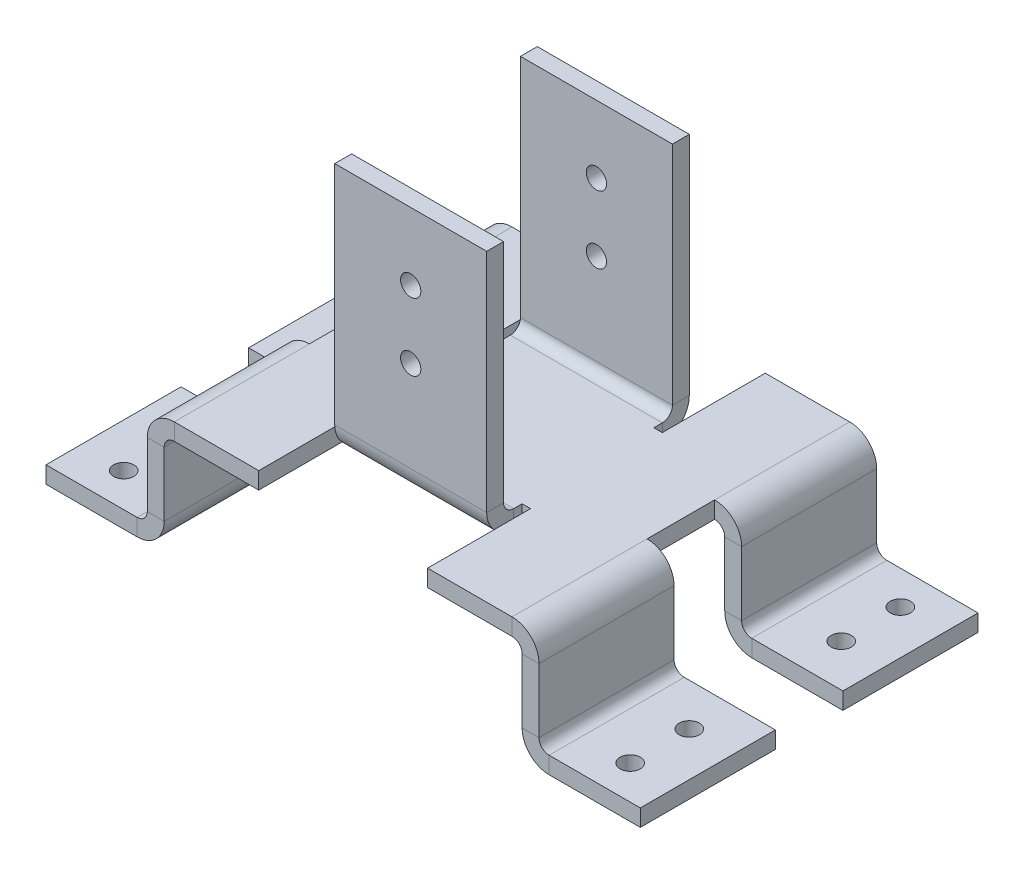
SolidWorks part; units mm, degrees
note: The reader was unsure of these and kept them because the rebuilt part matched: flange length of "边线-法兰1", "边线-法兰2", "边线-法兰14", "边线-法兰15", "边线-法兰16", "边线-法兰17", "边线-法兰18", "边线-法兰19", "边线-法兰20", "边线-法兰21".
ref_plane "前视基准面" through (0, 0, 0) normal (0, 0, 1) x (1, 0, 0)
ref_plane "上视基准面" through (0, 0, 0) normal (0, 1, 0) x (1, 0, 0)
ref_plane "右视基准面" through (0, 0, 0) normal (1, 0, 0) x (0, 0, -1)
other "Configuration Table"
sketch "草图1" plane through (0, 0, 0) normal (0, 1, 0) x (1, 0, 0)
  line L0 (-25, -25) -> (-25, -50)
  line L5 (-50, -50) -> (50, -50) construction
  line L6 (-50, -50) -> (-50, 50)
  line L11 (-50, 50) -> (50, 50) construction
  line L12 (50, -50) -> (50, 50)
  line L13 (-50, -50) -> (50, 50) construction
  line L14 (-50, 50) -> (50, -50) construction
  line L15 (-25, -25) -> (25, -25)
  line L16 (-25, -25) -> (-25, 25) construction
  line L17 (-25, 25) -> (25, 25)
  line L18 (25, -25) -> (25, 25) construction
  line L19 (-25, -25) -> (25, 25) construction
  line L20 (-25, 25) -> (25, -25) construction
  line L21 (-25, -50) -> (-50, -50)
  line L22 (25, -25) -> (25, -50)
  line L23 (25, -50) -> (50, -50)
  line L24 (-25, 25) -> (-25, 50)
  line L25 (-25, 50) -> (-50, 50)
  line L26 (25, 25) -> (25, 50)
  line L27 (25, 50) -> (50, 50)
  point P0 (0, 0)
  point P6 (0, 0)
  dimension "D1" = 100
  dimension "D2" = 100
  dimension "D3" = 50
base flange "基体-法兰1" sketch "草图1" thickness 5 reverse thickness direction no parameters "D1"=0.7366
edge flange "边线-法兰1" sketch "草图8" flange angle 90 flange length 75 flange position material outside bend radius 3 thickness 5 relief rectangular parameters "D6"=10
sketch "草图8" plane through (0, 0, -25) normal (0, 0, -1) x (-1, 0, 0)
  line L1 (-22.5, 0) -> (22.5, 0)
  line L2 (-22.5, 0) -> (-22.5, 70)
  line L3 (-22.5, 70) -> (22.5, 70)
  line L4 (22.5, 0) -> (22.5, 70)
  line L5 (-25, 0) -> (25, 0) construction
  point P6 (0, 70)
  dimension "D1" = 70
  dimension "D2" = 45
bend "边线折弯1" bend radius 3 bend angle 90 parameters "D5"=1
edge flange "边线-法兰2" sketch "草图11" flange angle 90 flange length 75 flange position material outside bend radius 3 thickness 5 relief rectangular parameters "D6"=10
sketch "草图11" plane through (0, 0, 25) normal (0, 0, 1) x (1, 0, 0)
  line L6 (-22.5, 70) -> (22.5, 70)
  line L7 (-22.5, 70) -> (-22.5, 0)
  line L8 (-22.5, 0) -> (22.5, 0)
  line L9 (22.5, 70) -> (22.5, 0)
bend "边线折弯2" bend radius 3 bend angle 90 parameters "D5"=2
edge flange "边线-法兰14" sketch "草图54" flange angle 90 flange length 35 flange position bend outside bend radius 3 thickness 5 relief rectangular parameters "D6"=10
sketch "草图54" plane through (50, -5, 0) normal (1, 0, 0) x (0, 0, 1)
  line L6 (50, 0) -> (10, 0)
  line L7 (50, 0) -> (50, 30)
  line L8 (50, 30) -> (10, 30)
  line L9 (10, 0) -> (10, 30)
  dimension "D1" = 30
  dimension "D2" = 40
bend "边线折弯12" bend radius 3 bend angle 90 parameters "D5"=3
edge flange "边线-法兰15" sketch "草图57" flange angle 90 flange length 35 flange position bend outside bend radius 3 thickness 5 relief rectangular parameters "D6"=10
sketch "草图57" plane through (50, -5, 0) normal (1, 0, 0) x (0, 0, 1)
  line L6 (-50, 0) -> (-10, 0)
  line L7 (-50, 0) -> (-50, 30)
  line L8 (-50, 30) -> (-10, 30)
  line L9 (-10, 0) -> (-10, 30)
  dimension "D1" = 40
  dimension "D2" = 30
bend "边线折弯13" bend radius 3 bend angle 90 parameters "D5"=4
edge flange "边线-法兰16" sketch "草图62" flange angle 90 flange length 35 flange position bend outside bend radius 3 thickness 5 relief rectangular parameters "D6"=10
sketch "草图62" plane through (-50, -5, 0) normal (-1, 0, 0) x (0, 0, -1)
  line L6 (50, 0) -> (10, 0)
  line L7 (50, 0) -> (50, 30)
  line L8 (50, 30) -> (10, 30)
  line L9 (10, 0) -> (10, 30)
bend "边线折弯14" bend radius 3 bend angle 90 parameters "D5"=5
edge flange "边线-法兰17" sketch "草图65" flange angle 90 flange length 35 flange position bend outside bend radius 3 thickness 5 relief rectangular parameters "D6"=10
sketch "草图65" plane through (-50, -5, 0) normal (-1, 0, 0) x (0, 0, -1)
  line L6 (-50, 0) -> (-10, 0)
  line L7 (-50, 0) -> (-50, 30)
  line L8 (-50, 30) -> (-10, 30)
  line L9 (-10, 0) -> (-10, 30)
bend "边线折弯15" bend radius 3 bend angle 90 parameters "D5"=6
edge flange "边线-法兰18" sketch "草图70" flange angle 90 flange length 35 bend radius 3 thickness 5 relief rectangular parameters "D6"=10
sketch "草图70" plane through (-58, -35, 0) normal (0, -1, 0) x (0, 0, 1)
  line L0 (-50, 0) -> (-10, 0) construction
  line L1 (-50, 0) -> (-10, 0)
  line L2 (-50, 0) -> (-50, 30)
  line L3 (-50, 30) -> (-10, 30)
  line L4 (-10, 30) -> (-10, 0)
  dimension "D1" = 30
bend "边线折弯16" bend radius 3 bend angle 90 parameters "D5"=7
edge flange "边线-法兰19" sketch "草图73" flange angle 90 flange length 35 bend radius 3 thickness 5 relief rectangular parameters "D6"=10
sketch "草图73" plane through (-58, -35, 0) normal (0, -1, 0) x (0, 0, 1)
  line L0 (10, 0) -> (50, 0) construction
  line L1 (10, 0) -> (50, 0)
  line L2 (10, 0) -> (10, 30)
  line L3 (10, 30) -> (50, 30)
  line L4 (50, 30) -> (50, 0)
  dimension "D1" = 30
bend "边线折弯17" bend radius 3 bend angle 90 parameters "D5"=8
edge flange "边线-法兰20" sketch "草图76" flange angle 90 flange length 35 bend radius 3 thickness 5 relief rectangular parameters "D6"=10
sketch "草图76" plane through (58, -35, 0) normal (0, -1, 0) x (0, 0, -1)
  line L0 (-50, 0) -> (-10, 0) construction
  line L1 (-50, 0) -> (-10, 0)
  line L2 (-50, 0) -> (-50, 30)
  line L3 (-50, 30) -> (-10, 30)
  line L4 (-10, 30) -> (-10, 0)
  dimension "D1" = 30
bend "边线折弯18" bend radius 3 bend angle 90 parameters "D5"=9
edge flange "边线-法兰21" sketch "草图79" flange angle 90 flange length 35 bend radius 3 thickness 5 relief rectangular parameters "D6"=10
sketch "草图79" plane through (58, -35, 0) normal (0, -1, 0) x (0, 0, -1)
  line L0 (10, 0) -> (50, 0) construction
  line L1 (10, 0) -> (50, 0)
  line L2 (10, 0) -> (10, 30)
  line L3 (10, 30) -> (50, 30)
  line L4 (50, 30) -> (50, 0)
  dimension "D1" = 30
bend "边线折弯19" bend radius 3 bend angle 90 parameters "D5"=10
sketch "草图80" plane through (0, 0, 0) normal (0, 1, 0) x (1, 0, 0)
  line L1 (-75, -40) -> (75, -40) construction
  line L2 (-75, -40) -> (-75, 40) construction
  line L3 (-75, 40) -> (75, 40) construction
  line L4 (75, -40) -> (75, 40) construction
  line L5 (-75, -40) -> (75, 40) construction
  line L6 (-75, 40) -> (75, -40) construction
  circle A0 centre (-75, 40) radius 3
  circle A1 centre (75, 40) radius 3
  circle A2 centre (-75, -40) radius 3
  circle A3 centre (75, -40) radius 3
  point P0 (0, 0)
  dimension "D3" = 6
  dimension "D4" = 6
  dimension "D5" = 6
  dimension "D6" = 6
  dimension "D1" = 80
  dimension "D2" = 150
extrude "切除-拉伸1" cut sketch "草图80" along normal up to surface (5 mm away) from surface at -35 up to face at (-74.5, -30, -30) starting at face at (-74.5, -35, -30)
sketch "草图83" plane through (0, 0, 0) normal (0, 0, 1) x (1, 0, 0)
  line L1 (-22.5, 70) -> (22.5, 70) construction
  line L2 (-22.5, 70) -> (-22.5, 10) construction
  line L3 (-22.5, 10) -> (22.5, 10) construction
  line L4 (22.5, 70) -> (22.5, 10) construction
  line L5 (-22.5, 70) -> (22.5, 10) construction
  line L6 (22.5, 70) -> (-22.5, 10) construction
  line L7 (0, 30) -> (0, 50) construction
  circle A0 centre (0, 50) radius 3
  circle A1 centre (0, 30) radius 3
  point P11 (0, 40)
  dimension "D3" = 6
  dimension "D4" = 6
  dimension "D1" = 60
  dimension "D2" = 20
extrude "切除-拉伸3" cut sketch "草图83" against normal through all and the other way through all normal cut yes
sketch "草图84" plane through (0, 0, 0) normal (0, 1, 0) x (1, 0, 0)
  line L1 (-75, -22.5) -> (75, -22.5) construction
  line L2 (-75, -22.5) -> (-75, 22.5) construction
  line L3 (-75, 22.5) -> (75, 22.5) construction
  line L4 (75, -22.5) -> (75, 22.5) construction
  line L5 (-75, -22.5) -> (75, 22.5) construction
  line L6 (-75, 22.5) -> (75, -22.5) construction
  circle A0 centre (75, 22.5) radius 3
  circle A1 centre (75, -22.5) radius 3
  circle A2 centre (-75, -22.5) radius 3
  circle A3 centre (-75, 22.5) radius 3
  point P0 (0, 0)
  dimension "D3" = 6
  dimension "D4" = 6
  dimension "D5" = 6
  dimension "D6" = 6
  dimension "D1" = 150
  dimension "D2" = 45
extrude "切除-拉伸5" cut sketch "草图84" against normal up to surface (5 mm away) from surface at -30 up to face at (-75, -35, 43) starting at face at (-75, -30, 43)
sketch "折弯-线1" plane through (0, 0, 0) normal (0, 1, 0) x (1, 0, 0)
sketch "边界框1" plane through (0, 0, 0) normal (0, 1, 0) x (1, 0, 0)
sheet metal parameters "钣金6" thickness 5 parameters "D1"=0.7366
flat pattern "平板型式6" [suppressed]
sketch "折弯-线2" plane through (0, 0, 0) normal (0, 1, 0) x (1, 0, 0)
sketch "边界框2" [suppressed] plane through (0, 0, 0) normal (0, 1, 0) x (1, 0, 0)
sheet metal parameters "钣金7" thickness 5 parameters "D1"=0.7366
flat pattern "平板型式6" [suppressed]
sketch "折弯-线2" plane through (0, 0, 0) normal (0, 1, 0) x (1, 0, 0)
sketch "边界框2" [suppressed] plane through (0, 0, 0) normal (0, 1, 0) x (1, 0, 0)
bend of the flat pattern "展平-<边线折弯1>1"
sheet metal parameters "钣金8" thickness 5 parameters "D1"=0.7366
flat pattern "平板型式6" [suppressed]
sketch "折弯-线2" plane through (0, 0, 0) normal (0, 1, 0) x (1, 0, 0)
sketch "边界框2" [suppressed] plane through (0, 0, 0) normal (0, 1, 0) x (1, 0, 0)
bend of the flat pattern "展平-<边线折弯1>1"
bend of the flat pattern "展平-<边线折弯2>1"
sheet metal parameters "钣金18" thickness 5 parameters "D1"=0.7366
flat pattern "平板型式6" [suppressed]
sketch "折弯-线2" plane through (0, 0, 0) normal (0, 1, 0) x (1, 0, 0)
sketch "边界框2" [suppressed] plane through (0, 0, 0) normal (0, 1, 0) x (1, 0, 0)
bend of the flat pattern "展平-<边线折弯1>1"
bend of the flat pattern "展平-<边线折弯2>1"
bend of the flat pattern "展平-<边线折弯12>1"
sheet metal parameters "钣金19" thickness 5 parameters "D1"=0.7366
flat pattern "平板型式6" [suppressed]
sketch "折弯-线2" plane through (0, 0, 0) normal (0, 1, 0) x (1, 0, 0)
sketch "边界框2" [suppressed] plane through (0, 0, 0) normal (0, 1, 0) x (1, 0, 0)
bend of the flat pattern "展平-<边线折弯1>1"
bend of the flat pattern "展平-<边线折弯2>1"
bend of the flat pattern "展平-<边线折弯13>1"
bend of the flat pattern "展平-<边线折弯12>1"
sheet metal parameters "钣金20" thickness 5 parameters "D1"=0.7366
flat pattern "平板型式6" [suppressed]
sketch "折弯-线2" plane through (0, 0, 0) normal (0, 1, 0) x (1, 0, 0)
sketch "边界框2" [suppressed] plane through (0, 0, 0) normal (0, 1, 0) x (1, 0, 0)
bend of the flat pattern "展平-<边线折弯1>1"
bend of the flat pattern "展平-<边线折弯2>1"
bend of the flat pattern "展平-<边线折弯13>1"
bend of the flat pattern "展平-<边线折弯14>1"
bend of the flat pattern "展平-<边线折弯12>1"
sheet metal parameters "钣金21" thickness 5 parameters "D1"=0.7366
flat pattern "平板型式6" [suppressed]
sketch "折弯-线2" plane through (0, 0, 0) normal (0, 1, 0) x (1, 0, 0)
sketch "边界框2" [suppressed] plane through (0, 0, 0) normal (0, 1, 0) x (1, 0, 0)
bend of the flat pattern "展平-<边线折弯1>1"
bend of the flat pattern "展平-<边线折弯2>1"
bend of the flat pattern "展平-<边线折弯13>1"
bend of the flat pattern "展平-<边线折弯14>1"
bend of the flat pattern "展平-<边线折弯15>1"
bend of the flat pattern "展平-<边线折弯12>1"
sheet metal parameters "钣金22" thickness 5 parameters "D1"=0.7366
flat pattern "平板型式6" [suppressed]
sketch "折弯-线2" plane through (0, 0, 0) normal (0, 1, 0) x (1, 0, 0)
sketch "边界框2" [suppressed] plane through (0, 0, 0) normal (0, 1, 0) x (1, 0, 0)
bend of the flat pattern "展平-<边线折弯1>1"
bend of the flat pattern "展平-<边线折弯2>1"
bend of the flat pattern "展平-<边线折弯13>1"
bend of the flat pattern "展平-<边线折弯14>1"
bend of the flat pattern "展平-<边线折弯15>1"
bend of the flat pattern "展平-<边线折弯12>1"
bend of the flat pattern "展平-<边线折弯16>1"
sheet metal parameters "钣金23" thickness 5 parameters "D1"=0.7366
flat pattern "平板型式6" [suppressed]
sketch "折弯-线2" plane through (0, 0, 0) normal (0, 1, 0) x (1, 0, 0)
sketch "边界框2" [suppressed] plane through (0, 0, 0) normal (0, 1, 0) x (1, 0, 0)
bend of the flat pattern "展平-<边线折弯1>1"
bend of the flat pattern "展平-<边线折弯2>1"
bend of the flat pattern "展平-<边线折弯13>1"
bend of the flat pattern "展平-<边线折弯14>1"
bend of the flat pattern "展平-<边线折弯15>1"
bend of the flat pattern "展平-<边线折弯12>1"
bend of the flat pattern "展平-<边线折弯17>1"
bend of the flat pattern "展平-<边线折弯16>1"
sheet metal parameters "钣金24" thickness 5 parameters "D1"=0.7366
flat pattern "平板型式6" [suppressed]
sketch "折弯-线2" plane through (0, 0, 0) normal (0, 1, 0) x (1, 0, 0)
sketch "边界框2" [suppressed] plane through (0, 0, 0) normal (0, 1, 0) x (1, 0, 0)
bend of the flat pattern "展平-<边线折弯1>1"
bend of the flat pattern "展平-<边线折弯2>1"
bend of the flat pattern "展平-<边线折弯13>1"
bend of the flat pattern "展平-<边线折弯14>1"
bend of the flat pattern "展平-<边线折弯15>1"
bend of the flat pattern "展平-<边线折弯12>1"
bend of the flat pattern "展平-<边线折弯17>1"
bend of the flat pattern "展平-<边线折弯18>1"
bend of the flat pattern "展平-<边线折弯16>1"
sheet metal parameters "钣金25" thickness 5 parameters "D1"=0.7366
flat pattern "平板型式6" [suppressed]
sketch "折弯-线2" plane through (0, 0, 0) normal (0, 1, 0) x (1, 0, 0)
sketch "边界框2" [suppressed] plane through (0, 0, 0) normal (0, 1, 0) x (1, 0, 0)
bend of the flat pattern "展平-<边线折弯1>1"
bend of the flat pattern "展平-<边线折弯2>1"
bend of the flat pattern "展平-<边线折弯13>1"
bend of the flat pattern "展平-<边线折弯14>1"
bend of the flat pattern "展平-<边线折弯15>1"
bend of the flat pattern "展平-<边线折弯12>1"
bend of the flat pattern "展平-<边线折弯17>1"
bend of the flat pattern "展平-<边线折弯18>1"
bend of the flat pattern "展平-<边线折弯19>1"
bend of the flat pattern "展平-<边线折弯16>1"
sheet metal parameters "钣金26" thickness 5 parameters "D1"=0.7366
flat pattern "平板型式6" [suppressed]
sketch "折弯-线2" plane through (0, 0, 0) normal (0, 1, 0) x (1, 0, 0)
sketch "边界框2" [suppressed] plane through (0, 0, 0) normal (0, 1, 0) x (1, 0, 0)
bend of the flat pattern "展平-<边线折弯1>1"
bend of the flat pattern "展平-<边线折弯2>1"
bend of the flat pattern "展平-<边线折弯13>1"
bend of the flat pattern "展平-<边线折弯14>1"
bend of the flat pattern "展平-<边线折弯15>1"
bend of the flat pattern "展平-<边线折弯12>1"
bend of the flat pattern "展平-<边线折弯17>1"
bend of the flat pattern "展平-<边线折弯18>1"
bend of the flat pattern "展平-<边线折弯19>1"
bend of the flat pattern "展平-<边线折弯16>1"
sheet metal parameters "钣金28" thickness 5 parameters "D1"=0.7366
flat pattern "平板型式6" [suppressed]
sketch "折弯-线2" plane through (0, 0, 0) normal (0, 1, 0) x (1, 0, 0)
sketch "边界框2" [suppressed] plane through (0, 0, 0) normal (0, 1, 0) x (1, 0, 0)
bend of the flat pattern "展平-<边线折弯1>1"
bend of the flat pattern "展平-<边线折弯2>1"
bend of the flat pattern "展平-<边线折弯13>1"
bend of the flat pattern "展平-<边线折弯14>1"
bend of the flat pattern "展平-<边线折弯15>1"
bend of the flat pattern "展平-<边线折弯12>1"
bend of the flat pattern "展平-<边线折弯17>1"
bend of the flat pattern "展平-<边线折弯18>1"
bend of the flat pattern "展平-<边线折弯19>1"
bend of the flat pattern "展平-<边线折弯16>1"
sheet metal parameters "钣金29" thickness 5 parameters "D1"=0.7366
flat pattern "平板型式6" [suppressed]
sketch "折弯-线2" plane through (0, 0, 0) normal (0, 1, 0) x (1, 0, 0)
sketch "边界框2" [suppressed] plane through (0, 0, 0) normal (0, 1, 0) x (1, 0, 0)
bend of the flat pattern "展平-<边线折弯1>1"
bend of the flat pattern "展平-<边线折弯2>1"
bend of the flat pattern "展平-<边线折弯13>1"
bend of the flat pattern "展平-<边线折弯14>1"
bend of the flat pattern "展平-<边线折弯15>1"
bend of the flat pattern "展平-<边线折弯12>1"
bend of the flat pattern "展平-<边线折弯17>1"
bend of the flat pattern "展平-<边线折弯18>1"
bend of the flat pattern "展平-<边线折弯19>1"
bend of the flat pattern "展平-<边线折弯16>1"
